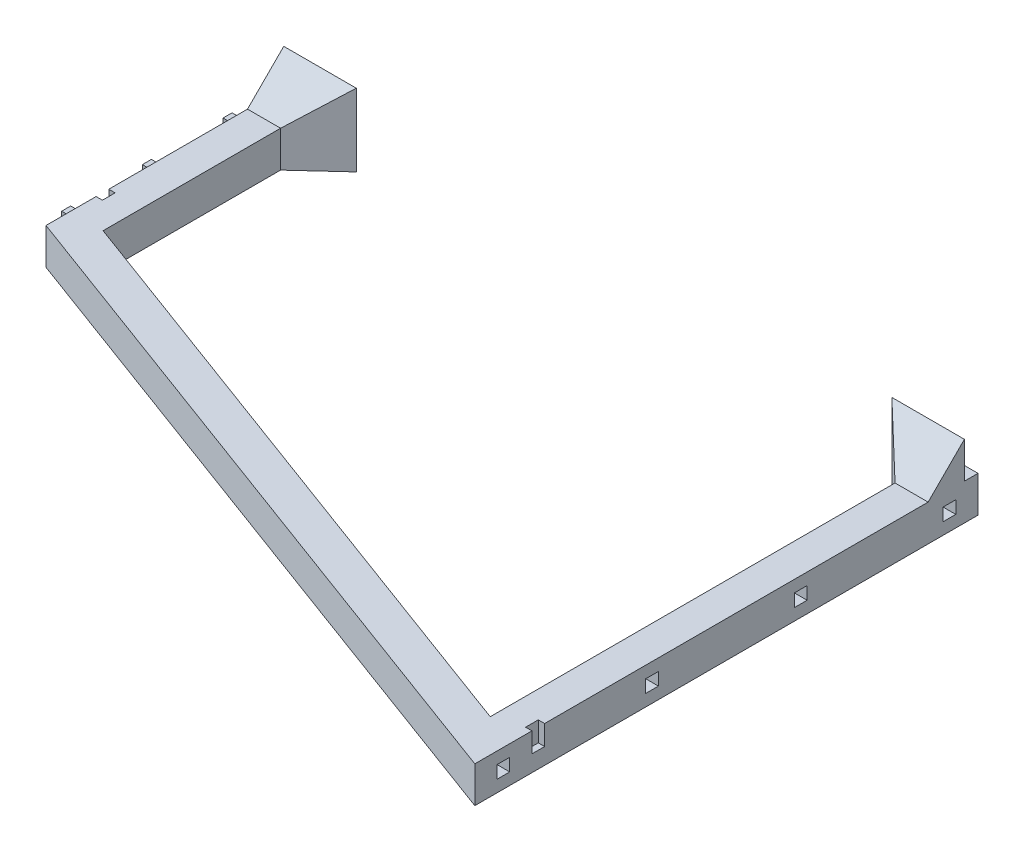
SolidWorks part; units mm, degrees
ref_plane "Přední rovina" through (0, 0, 0) normal (0, 0, 1) x (1, 0, 0)
ref_plane "Horní rovina" through (0, 0, 0) normal (0, 1, 0) x (1, 0, 0)
ref_plane "Pravá rovina" through (0, 0, 0) normal (1, 0, 0) x (0, 0, -1)
sketch "Skica1" plane through (0, 0, 0) normal (0, 1, 0) x (1, 0, 0)
  line L0 (0, 0) -> (0, -111)
  line L1 (0, -111) -> (-150.15, -55.45)
  line L2 (-150.15, -55.45) -> (-150.15, 0)
  line L3 (-150.15, 0) -> (-142.85, 0)
  line L4 (-142.85, 0) -> (-142.85, -50.1539)
  line L5 (-142.85, -50.1539) -> (-7.3, -100.3024)
  line L6 (-7.3, -100.3024) -> (-7.3, 0)
  line L7 (-7.3, 0) -> (0, 0)
  dimension "D1" = 111
  dimension "D2" = 7.3
  dimension "D3" = 7.3
  dimension "D4" = 150.15
  dimension "D5" = 7.5
  dimension "D6" = 55.45
extrude "Přidat vysunutím1" add sketch "Skica1" along normal blind 8
sketch "Skica3" plane through (0, 8, 0) normal (0, 1, 0) x (1, 0, 0)
  line L0 (0, -111) -> (0, 0) construction
  line L1 (0, -95.6) -> (-1.4, -95.6)
  line L2 (0, -95.6) -> (0, -98.4)
  line L3 (0, -98.4) -> (-1.4, -98.4)
  line L4 (-1.4, -95.6) -> (-1.4, -98.4)
  dimension "D1" = 2.8
  dimension "D2" = 1.4
  dimension "D3" = 12.6
extrude "Odebrat vysunutím1" cut sketch "Skica3" against normal blind 4.4
sketch "Skica6" plane through (0, 8, 0) normal (0, 1, 0) x (1, 0, 0)
  line L0 (-150.15, 0) -> (-150.15, -55.45) construction
  line L9 (-150.15, -3) -> (-134.15, -3)
  line L10 (-150.15, -3) -> (-150.15, -11)
  line L11 (-150.15, -11) -> (-134.15, -11)
  line L12 (-134.15, -3) -> (-134.15, -11)
  line L13 (-142.85, 0) -> (-150.15, 0) construction
  line L14 (0, -95.6) -> (0, 0) construction
  line L15 (0, -3) -> (-16, -3)
  line L16 (0, -3) -> (0, -11)
  line L17 (0, -11) -> (-16, -11)
  line L18 (-16, -3) -> (-16, -11)
  line L19 (0, 0) -> (-7.3, 0) construction
  dimension "D1" = 3
  dimension "D2" = 16
  dimension "D3" = 3
  dimension "D4" = 8
  dimension "D5" = 16
  dimension "D6" = 8
extrude "Přidat vysunutím3" add sketch "Skica6" against normal blind 16 from offset 8 contours L15 L18 L17 L16 | L9 L12 L11 L10
sketch "Skica8" plane through (0, 0, 0) normal (1, 0, 0) x (0, 0, -1)
  line L3 (-11, 8) -> (-11, 16)
  line L4 (-11, 16) -> (-3, 16)
  line L5 (-3, 16) -> (-11, 8)
extrude "Odebrat vysunutím3" cut sketch "Skica8" against normal through all
sketch "Skica9" plane through (0, 0, 0) normal (0, -1, 0) x (1, 0, 0)
  line L8 (-142.85, 11) -> (-134.15, 11)
  line L9 (-134.15, 11) -> (-134.15, 3)
  line L10 (-134.15, 3) -> (-142.85, 11)
  line L11 (-16, 11) -> (-7.3, 11)
  line L12 (-7.3, 11) -> (-16, 3)
  line L13 (-16, 3) -> (-16, 11)
extrude "Odebrat vysunutím4" cut sketch "Skica9" against normal through all
sketch "Skica4" plane through (0, 0, 0) normal (1, 0, 0) x (0, 0, -1)
  line L0 (-111, 8) -> (-98.4, 8) construction
  line L1 (-106.1, 5.4) -> (-103.3, 5.4)
  line L2 (-106.1, 5.4) -> (-106.1, 2.6)
  line L3 (-106.1, 2.6) -> (-103.3, 2.6)
  line L4 (-103.3, 5.4) -> (-103.3, 2.6)
  line L22 (-73.3, 5.4) -> (-70.5, 5.4)
  line L23 (-73.3, 5.4) -> (-73.3, 2.6)
  line L24 (-73.3, 2.6) -> (-70.5, 2.6)
  line L25 (-70.5, 5.4) -> (-70.5, 2.6)
  line L26 (-40.5, 5.4) -> (-37.7, 5.4)
  line L27 (-40.5, 5.4) -> (-40.5, 2.6)
  line L28 (-40.5, 2.6) -> (-37.7, 2.6)
  line L29 (-37.7, 5.4) -> (-37.7, 2.6)
  line L30 (-7.7, 5.4) -> (-4.9, 5.4)
  line L31 (-7.7, 5.4) -> (-7.7, 2.6)
  line L32 (-7.7, 2.6) -> (-4.9, 2.6)
  line L33 (-4.9, 5.4) -> (-4.9, 2.6)
  line L34 (-95.6, 8) -> (-11, 8) construction
  line L35 (-111, 0) -> (0, 0) construction
  line L37 (0, 8) -> (0, 0) construction
  point P18 (-6.3, 2.6)
  dimension "D1" = 2.8
  dimension "D2" = 2.8
  dimension "D3" = 2.6
  dimension "D4" = 4.9
  dimension "D5" = 2.8
  dimension "D6" = 2.8
  dimension "D7" = 2.6
  dimension "D8" = 30
  dimension "D9" = 30
  dimension "D10" = 2.8
  dimension "D11" = 2.8
  dimension "D12" = 2.6
  dimension "D13" = 2.6
  dimension "D14" = 2.8
  dimension "D15" = 2.8
  dimension "D16" = 30
extrude "Odebrat vysunutím2" cut sketch "Skica4" against normal blind 4.4
sketch "Skica5" plane through (-150.15, 0, 0) normal (-1, 0, 0) x (0, 0, 1)
  line L0 (0, 8) -> (3, 8) construction
  line L1 (10.4, 5) -> (12.4, 5)
  line L2 (10.4, 5) -> (10.4, 3)
  line L3 (10.4, 3) -> (12.4, 3)
  line L4 (12.4, 5) -> (12.4, 3)
  line L5 (28.2, 5) -> (30.2, 5)
  line L6 (28.2, 5) -> (28.2, 3)
  line L7 (28.2, 3) -> (30.2, 3)
  line L8 (30.2, 5) -> (30.2, 3)
  line L9 (0, 8) -> (0, 0) construction
  line L11 (46, 5) -> (48, 5)
  line L12 (46, 5) -> (46, 3)
  line L13 (46, 3) -> (48, 3)
  line L14 (48, 5) -> (48, 3)
  dimension "D1" = 2
  dimension "D2" = 2
  dimension "D3" = 3
  dimension "D4" = 10.4
  dimension "D5" = 15.8
  dimension "D6" = 2
  dimension "D7" = 2
  dimension "D8" = 3
  dimension "D9" = 15.8
  dimension "D10" = 2
  dimension "D11" = 2
  dimension "D12" = 3
extrude "Přidat vysunutím2" add sketch "Skica5" along normal blind 4
sketch "Skica10" plane through (0, 8, 0) normal (0, 1, 0) x (1, 0, 0)
  line L0 (-150.15, -11) -> (-150.15, -55.45) construction
  line L1 (-150.15, -41.6) -> (-148.75, -41.6)
  line L2 (-150.15, -41.6) -> (-150.15, -44.4)
  line L3 (-150.15, -44.4) -> (-148.75, -44.4)
  line L4 (-148.75, -41.6) -> (-148.75, -44.4)
  line L5 (-142.85, 0) -> (-150.15, 0) construction
  dimension "D1" = 41.6
  dimension "D2" = 2.8
  dimension "D3" = 1.4
extrude "Odebrat vysunutím5" cut sketch "Skica10" against normal blind 4.4
